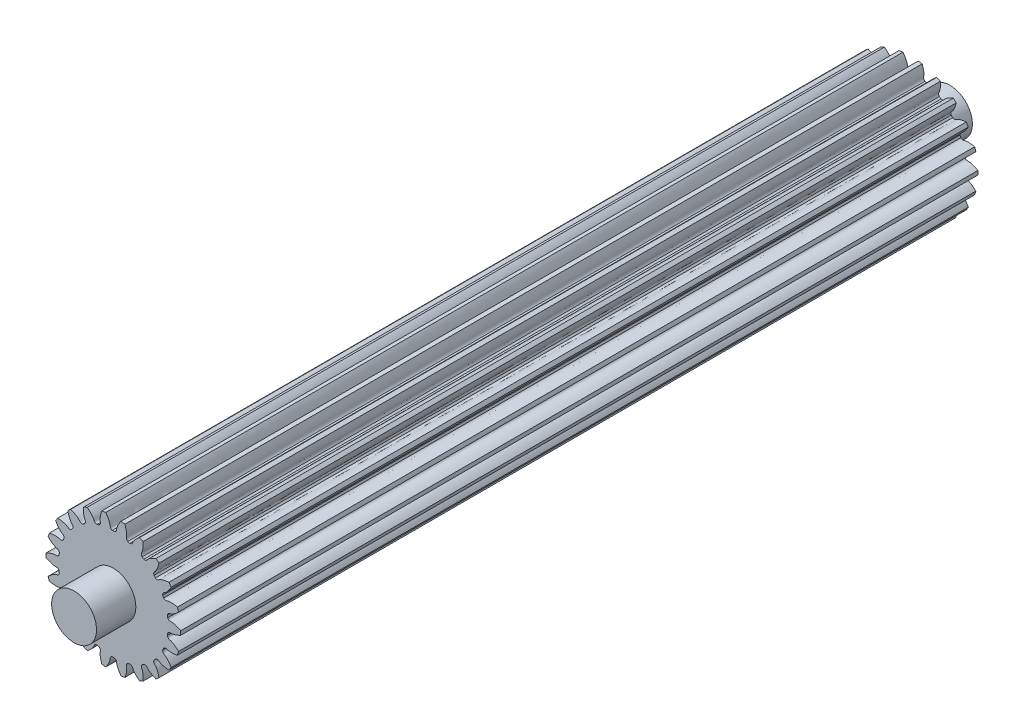
SolidWorks part; units mm, degrees
ref_plane "前视基准面" through (0, 0, 0) normal (0, 0, 1) x (1, 0, 0)
ref_plane "上视基准面" through (0, 0, 0) normal (0, 1, 0) x (1, 0, 0)
ref_plane "右视基准面" through (0, 0, 0) normal (1, 0, 0) x (0, 0, -1)
sketch "草图1" plane through (0, 0, 0) normal (0, 0, 1) x (1, 0, 0)
  circle A0 centre (0, 0) radius 12
extrude "凸台-拉伸1" add sketch "草图1" along normal blind 30
ref_axis "基准轴1" through (0, 0, -1.5) along (0, 0, 1)
sketch "草图2" plane through (0, 0, 0) normal (0, 0, 1) x (1, 0, 0)
  line L0 (0, 0) -> (0, 12) construction
  circle A0 centre (0, 0) radius 12 construction
  arc A1 (0.1857, 9.7482) -> (-0.1857, 9.7482) centre (0, 0) ccw
  arc A2 (3.0856, 13.5599) -> (-3.0856, 13.5599) centre (0, 0) ccw
  spline S0 degree 3 poles (0.1857, 9.7482) (0.5882, 9.8762) (0.5483, 10.1518) (0.5996, 10.4216) (0.606, 10.4519) (0.6139, 10.4862) (0.6235, 10.5243) (0.6349, 10.5661) (0.6484, 10.6117) (0.664, 10.661) (0.6819, 10.7139) (0.7023, 10.7703) (0.7253, 10.8301) (0.7511, 10.8933) (0.7797, 10.9597) (0.8114, 11.0293) (0.8462, 11.1021) (0.8843, 11.1778) (0.9259, 11.2563) (0.9711, 11.3377) (1.0199, 11.4217) (1.0726, 11.5082) (1.1292, 11.5972) (1.1899, 11.6884) (1.2547, 11.7818) (1.3238, 11.8773) (1.3973, 11.9746) (1.4753, 12.0737) (1.5579, 12.1744) (1.6452, 12.2766) (1.7372, 12.3802) (1.8341, 12.4849) (1.9359, 12.5906) (2.0428, 12.6972) (2.1547, 12.8044) (2.2718, 12.9123) (2.3942, 13.0205) (2.5218, 13.1289) (2.6548, 13.2373) (2.8415, 13.3834) (2.9864, 13.49) (3.0856, 13.5599) knots 0 0 0 0 0.157021 0.162531 0.168888 0.176093 0.184146 0.193046 0.202794 0.213389 0.224833 0.237123 0.250262 0.264248 0.279082 0.294763 0.311292 0.328669 0.346893 0.365965 0.385884 0.406652 0.428266 0.450729 0.474039 0.498197 0.523202 0.549055 0.575756 0.603304 0.6317 0.660944 0.691035 0.721974 0.75376 0.786395 0.819876 0.854206 0.889383 0.925408 1 1 1 1
  spline S1 degree 3 poles (-0.1857, 9.7482) (-0.5882, 9.8762) (-0.5483, 10.1518) (-0.5996, 10.4216) (-0.606, 10.4519) (-0.6139, 10.4862) (-0.6235, 10.5243) (-0.6349, 10.5661) (-0.6484, 10.6117) (-0.664, 10.661) (-0.6819, 10.7139) (-0.7023, 10.7703) (-0.7253, 10.8301) (-0.7511, 10.8933) (-0.7797, 10.9597) (-0.8114, 11.0293) (-0.8462, 11.1021) (-0.8843, 11.1778) (-0.9259, 11.2563) (-0.9711, 11.3377) (-1.0199, 11.4217) (-1.0726, 11.5082) (-1.1292, 11.5972) (-1.1899, 11.6884) (-1.2547, 11.7818) (-1.3238, 11.8773) (-1.3973, 11.9746) (-1.4753, 12.0737) (-1.5579, 12.1744) (-1.6452, 12.2766) (-1.7372, 12.3802) (-1.8341, 12.4849) (-1.9359, 12.5906) (-2.0428, 12.6972) (-2.1547, 12.8044) (-2.2718, 12.9123) (-2.3942, 13.0205) (-2.5218, 13.1289) (-2.6548, 13.2373) (-2.8415, 13.3834) (-2.9864, 13.49) (-3.0856, 13.5599) knots 0 0 0 0 0.157021 0.162531 0.168888 0.176093 0.184146 0.193046 0.202794 0.213389 0.224833 0.237123 0.250262 0.264248 0.279082 0.294763 0.311292 0.328669 0.346893 0.365965 0.385884 0.406652 0.428266 0.450729 0.474039 0.498197 0.523202 0.549055 0.575756 0.603304 0.6317 0.660944 0.691035 0.721974 0.75376 0.786395 0.819876 0.854206 0.889383 0.925408 1 1 1 1
extrude "切除-拉伸1" cut sketch "草图2" along normal through all
pattern_circular "阵列(圆周)1" count 22 every 16.364 about axis through (0, 0, -1.5) along (0, 0, 1) of "切除-拉伸1"
sketch "草图3" plane through (0, 0, 0) normal (0, 0, 1) x (1, 0, 0)
  circle A0 centre (0, 0) radius 11 construction
  dimension "Dn" = 22
sketch "草图4" plane through (0, 0, 0) normal (0, 0, -1) x (-1, 0, 0)
  arc A45 (2.9245, 9.3011) -> (2.5682, 9.4057) centre (0, 0) ccw
  arc A46 (2.0557, 11.8226) -> (1.3584, 11.9229) centre (0, 0) ccw
  arc A47 (0.1857, 9.7482) -> (-0.1857, 9.7482) centre (0, 0) ccw
  arc A48 (-1.3584, 11.9229) -> (-2.0557, 11.8226) centre (0, 0) ccw
  arc A49 (-2.5682, 9.4057) -> (-2.9245, 9.3011) centre (0, 0) ccw
  arc A50 (-4.6624, 11.0572) -> (-5.3032, 10.7646) centre (0, 0) ccw
  arc A51 (-5.1141, 8.3011) -> (-5.4265, 8.1004) centre (0, 0) ccw
  arc A52 (-7.5887, 9.2958) -> (-8.1211, 8.8344) centre (0, 0) ccw
  arc A53 (-7.2456, 6.5241) -> (-7.4888, 6.2434) centre (0, 0) ccw
  arc A54 (-9.9003, 6.7812) -> (-10.2811, 6.1886) centre (0, 0) ccw
  arc A55 (-8.7902, 4.2184) -> (-8.9444, 3.8807) centre (0, 0) ccw
  arc A56 (-11.4097, 3.7173) -> (-11.6082, 3.0414) centre (0, 0) ccw
  arc A57 (-9.6226, 1.5711) -> (-9.6754, 1.2035) centre (0, 0) ccw
  arc A58 (-11.9948, 0.3522) -> (-11.9948, -0.3522) centre (0, 0) ccw
  arc A59 (-9.6754, -1.2035) -> (-9.6226, -1.5711) centre (0, 0) ccw
  arc A60 (-11.6082, -3.0414) -> (-11.4097, -3.7173) centre (0, 0) ccw
  arc A61 (-8.9444, -3.8807) -> (-8.7902, -4.2184) centre (0, 0) ccw
  arc A62 (-10.2811, -6.1886) -> (-9.9003, -6.7812) centre (0, 0) ccw
  arc A63 (-7.4888, -6.2434) -> (-7.2456, -6.5241) centre (0, 0) ccw
  arc A64 (-8.1211, -8.8344) -> (-7.5887, -9.2958) centre (0, 0) ccw
  arc A65 (-5.4265, -8.1004) -> (-5.1141, -8.3011) centre (0, 0) ccw
  arc A66 (-5.3032, -10.7646) -> (-4.6624, -11.0572) centre (0, 0) ccw
  arc A67 (-2.9245, -9.3011) -> (-2.5682, -9.4057) centre (0, 0) ccw
  arc A68 (-2.0557, -11.8226) -> (-1.3584, -11.9229) centre (0, 0) ccw
  arc A69 (-0.1857, -9.7482) -> (0.1857, -9.7482) centre (0, 0) ccw
  arc A70 (1.3584, -11.9229) -> (2.0557, -11.8226) centre (0, 0) ccw
  arc A71 (2.5682, -9.4057) -> (2.9245, -9.3011) centre (0, 0) ccw
  arc A72 (4.6624, -11.0572) -> (5.3032, -10.7646) centre (0, 0) ccw
  arc A73 (5.1141, -8.3011) -> (5.4265, -8.1004) centre (0, 0) ccw
  arc A74 (7.5887, -9.2958) -> (8.1211, -8.8344) centre (0, 0) ccw
  arc A75 (7.2456, -6.5241) -> (7.4888, -6.2434) centre (0, 0) ccw
  arc A76 (9.9003, -6.7812) -> (10.2811, -6.1886) centre (0, 0) ccw
  arc A77 (8.7902, -4.2184) -> (8.9444, -3.8807) centre (0, 0) ccw
  arc A78 (11.4097, -3.7173) -> (11.6082, -3.0414) centre (0, 0) ccw
  arc A79 (9.6226, -1.5711) -> (9.6754, -1.2035) centre (0, 0) ccw
  arc A80 (11.9948, -0.3522) -> (11.9948, 0.3522) centre (0, 0) ccw
  arc A81 (9.6754, 1.2035) -> (9.6226, 1.5711) centre (0, 0) ccw
  arc A82 (11.6082, 3.0414) -> (11.4097, 3.7173) centre (0, 0) ccw
  arc A83 (8.9444, 3.8807) -> (8.7902, 4.2184) centre (0, 0) ccw
  arc A84 (10.2811, 6.1886) -> (9.9003, 6.7812) centre (0, 0) ccw
  arc A85 (7.4888, 6.2434) -> (7.2456, 6.5241) centre (0, 0) ccw
  arc A86 (8.1211, 8.8344) -> (7.5887, 9.2958) centre (0, 0) ccw
  arc A87 (5.4265, 8.1004) -> (5.1141, 8.3011) centre (0, 0) ccw
  arc A88 (5.3032, 10.7646) -> (4.6624, 11.0572) centre (0, 0) ccw
  arc A89 (2.9245, 9.3011) -> (2.5682, 9.4057) centre (0, 0) ccw
  arc A90 (2.0557, 11.8226) -> (1.3584, 11.9229) centre (0, 0) ccw
  arc A91 (0.1857, 9.7482) -> (-0.1857, 9.7482) centre (0, 0) ccw
  arc A92 (-1.3584, 11.9229) -> (-2.0557, 11.8226) centre (0, 0) ccw
  arc A93 (-2.5682, 9.4057) -> (-2.9245, 9.3011) centre (0, 0) ccw
  arc A94 (-4.6624, 11.0572) -> (-5.3032, 10.7646) centre (0, 0) ccw
  arc A95 (-5.1141, 8.3011) -> (-5.4265, 8.1004) centre (0, 0) ccw
  arc A96 (-7.5887, 9.2958) -> (-8.1211, 8.8344) centre (0, 0) ccw
  arc A97 (-7.2456, 6.5241) -> (-7.4888, 6.2434) centre (0, 0) ccw
  arc A98 (-9.9003, 6.7812) -> (-10.2811, 6.1886) centre (0, 0) ccw
  arc A99 (-8.7902, 4.2184) -> (-8.9444, 3.8807) centre (0, 0) ccw
  arc A100 (-11.4097, 3.7173) -> (-11.6082, 3.0414) centre (0, 0) ccw
  arc A101 (-9.6226, 1.5711) -> (-9.6754, 1.2035) centre (0, 0) ccw
  arc A102 (-11.9948, 0.3522) -> (-11.9948, -0.3522) centre (0, 0) ccw
  arc A103 (-9.6754, -1.2035) -> (-9.6226, -1.5711) centre (0, 0) ccw
  arc A104 (-11.6082, -3.0414) -> (-11.4097, -3.7173) centre (0, 0) ccw
  arc A105 (-8.9444, -3.8807) -> (-8.7902, -4.2184) centre (0, 0) ccw
  arc A106 (-10.2811, -6.1886) -> (-9.9003, -6.7812) centre (0, 0) ccw
  arc A107 (-7.4888, -6.2434) -> (-7.2456, -6.5241) centre (0, 0) ccw
  arc A108 (-8.1211, -8.8344) -> (-7.5887, -9.2958) centre (0, 0) ccw
  arc A109 (-5.4265, -8.1004) -> (-5.1141, -8.3011) centre (0, 0) ccw
  arc A110 (-5.3032, -10.7646) -> (-4.6624, -11.0572) centre (0, 0) ccw
  arc A111 (-2.9245, -9.3011) -> (-2.5682, -9.4057) centre (0, 0) ccw
  arc A112 (-2.0557, -11.8226) -> (-1.3584, -11.9229) centre (0, 0) ccw
  arc A113 (-0.1857, -9.7482) -> (0.1857, -9.7482) centre (0, 0) ccw
  arc A114 (1.3584, -11.9229) -> (2.0557, -11.8226) centre (0, 0) ccw
  arc A115 (2.5682, -9.4057) -> (2.9245, -9.3011) centre (0, 0) ccw
  arc A116 (4.6624, -11.0572) -> (5.3032, -10.7646) centre (0, 0) ccw
  arc A117 (5.1141, -8.3011) -> (5.4265, -8.1004) centre (0, 0) ccw
  arc A118 (7.5887, -9.2958) -> (8.1211, -8.8344) centre (0, 0) ccw
  arc A119 (7.2456, -6.5241) -> (7.4888, -6.2434) centre (0, 0) ccw
  arc A120 (9.9003, -6.7812) -> (10.2811, -6.1886) centre (0, 0) ccw
  arc A121 (8.7902, -4.2184) -> (8.9444, -3.8807) centre (0, 0) ccw
  arc A122 (11.4097, -3.7173) -> (11.6082, -3.0414) centre (0, 0) ccw
  arc A123 (9.6226, -1.5711) -> (9.6754, -1.2035) centre (0, 0) ccw
  arc A124 (11.9948, -0.3522) -> (11.9948, 0.3522) centre (0, 0) ccw
  arc A125 (9.6754, 1.2035) -> (9.6226, 1.5711) centre (0, 0) ccw
  arc A126 (11.6082, 3.0414) -> (11.4097, 3.7173) centre (0, 0) ccw
  arc A127 (8.9444, 3.8807) -> (8.7902, 4.2184) centre (0, 0) ccw
  arc A128 (10.2811, 6.1886) -> (9.9003, 6.7812) centre (0, 0) ccw
  arc A129 (7.4888, 6.2434) -> (7.2456, 6.5241) centre (0, 0) ccw
  arc A130 (8.1211, 8.8344) -> (7.5887, 9.2958) centre (0, 0) ccw
  arc A131 (5.4265, 8.1004) -> (5.1141, 8.3011) centre (0, 0) ccw
  arc A132 (5.3032, 10.7646) -> (4.6624, 11.0572) centre (0, 0) ccw
  spline S44 degree 3 poles (-5627.2854, 2078.3938) (192.8946, -127.0066) (26.4411, 29.7149) (4.2738, 10.7434) (4.1283, 10.6084) (3.9999, 10.4794) (3.888, 10.3576) (3.7917, 10.2441) (3.7102, 10.1398) (3.6518, 10.0587) (3.6037, 9.9872) (3.5713, 9.9359) (3.5381, 9.8795) (3.5167, 9.8409) (0.8972, 4.7255) (36.3074, -19.3341) (-5049.4514, 3243.9843) knots -17.307157 -17.307157 -17.307157 -17.307157 0.549271 0.593348 0.634035 0.671331 0.705237 0.735752 0.762877 0.786611 0.797206 0.815854 0.823907 0.837469 0.842979 4.358372 4.358372 4.358372 4.358372 only from (4.6624, 11.0572) to (2.9245, 9.3011)
  spline S45 degree 3 poles (6000.7137, -0.9256) (-40.9919, 3.3645) (1.8001, 4.4607) (2.3619, 10.18) (2.3658, 10.2385) (2.3681, 10.3211) (2.3668, 10.4204) (2.3608, 10.536) (2.3486, 10.6678) (2.329, 10.8154) (2.3007, 10.9784) (2.2624, 11.1562) (2.213, 11.3485) (2.1511, 11.5544) (-7.9452, 40.8705) (-242.4769, -12.2249) (5863.0962, -1268.8283) knots -3.358181 -3.358181 -3.358181 -3.358181 0.157021 0.162531 0.176093 0.193046 0.213389 0.237123 0.264248 0.294763 0.328669 0.365965 0.406652 0.450729 0.498197 19.472301 19.472301 19.472301 19.472301 only from (2.5682, 9.4057) to (2.0557, 11.8226)
  spline S46 degree 3 poles (-5984.892, 408.8148) (220.863, -67.5173) (16.9983, 35.9606) (1.0739, 11.5123) (0.9723, 11.3417) (0.8855, 11.1818) (0.8124, 11.0334) (0.752, 10.8973) (0.7032, 10.7743) (0.6701, 10.6801) (0.644, 10.5979) (0.6274, 10.5396) (0.6113, 10.4761) (0.6018, 10.4331) (-0.4705, 4.7868) (40.2837, -8.322) (-5758.8491, 1689.9853) knots -17.307157 -17.307157 -17.307157 -17.307157 0.549271 0.593348 0.634035 0.671331 0.705237 0.735752 0.762877 0.786611 0.797206 0.815854 0.823907 0.837469 0.842979 4.358372 4.358372 4.358372 4.358372 only from (1.3584, 11.9229) to (0.1857, 9.7482)
  spline S47 degree 3 poles (5757.9034, 1689.7083) (-40.2793, -8.3206) (0.4704, 4.7871) (-0.6018, 10.4331) (-0.6145, 10.4903) (-0.6356, 10.5702) (-0.6648, 10.6651) (-0.7032, 10.7743) (-0.752, 10.8973) (-0.8124, 11.0334) (-0.8855, 11.1818) (-0.9723, 11.3417) (-1.0739, 11.5123) (-1.1913, 11.6924) (-19.1379, 36.9765) (-229.2107, -80.0433) (5983.0699, 434.3932) knots -3.358181 -3.358181 -3.358181 -3.358181 0.157021 0.162531 0.176093 0.193046 0.213389 0.237123 0.264248 0.294763 0.328669 0.365965 0.406652 0.450729 0.498197 19.472301 19.472301 19.472301 19.472301 only from (-0.1857, 9.7482) to (-1.3584, 11.9229)
  spline S48 degree 3 poles (-5857.6382, -1293.884) (230.9383, -2.5581) (6.1785, 39.2929) (-2.213, 11.3485) (-2.2624, 11.1562) (-2.3007, 10.9784) (-2.329, 10.8154) (-2.3486, 10.6678) (-2.3608, 10.536) (-2.366, 10.4362) (-2.3678, 10.3501) (-2.3674, 10.2894) (-2.3649, 10.224) (-2.3619, 10.18) (-1.8001, 4.4604) (40.9965, 3.3643) (-6001.6991, -0.9263) knots -17.307157 -17.307157 -17.307157 -17.307157 0.549271 0.593348 0.634035 0.671331 0.705237 0.735752 0.762877 0.786611 0.797206 0.815854 0.823907 0.837469 0.842979 4.358372 4.358372 4.358372 4.358372 only from (-2.0557, 11.8226) to (-2.5682, 9.4057)
  spline S49 degree 3 poles (5048.622, 3243.4521) (-36.3035, -19.3315) (-0.8973, 4.7258) (-3.5167, 9.8409) (-3.5451, 9.8922) (-3.5879, 9.963) (-3.6426, 10.0458) (-3.7102, 10.1398) (-3.7917, 10.2441) (-3.888, 10.3576) (-3.9999, 10.4794) (-4.1283, 10.6084) (-4.2738, 10.7434) (-4.4372, 10.8832) (-28.7802, 30.087) (-197.3753, -141.3771) (5618.3308, 2102.4228) knots -3.358181 -3.358181 -3.358181 -3.358181 0.157021 0.162531 0.176093 0.193046 0.213389 0.237123 0.264248 0.294763 0.328669 0.365965 0.406652 0.450729 0.498197 19.472301 19.472301 19.472301 19.472301 only from (-2.9245, 9.3011) to (-4.6624, 11.0572)
  spline S50 degree 3 poles (-5255.8335, -2891.76) (222.3043, 62.6084) (-5.1418, 39.442) (-5.3206, 10.2653) (-5.3138, 10.0669) (-5.3004, 9.8855) (-5.2817, 9.7211) (-5.2589, 9.574) (-5.2335, 9.4441) (-5.2104, 9.3469) (-5.1879, 9.2637) (-5.1704, 9.2057) (-5.1495, 9.1436) (-5.1343, 9.1022) (-2.9838, 3.7726) (38.388, 14.7781) (-5758.3272, -1691.7628) knots -17.307157 -17.307157 -17.307157 -17.307157 0.549271 0.593348 0.634035 0.671331 0.705237 0.735752 0.762877 0.786611 0.797206 0.815854 0.823907 0.837469 0.842979 4.358372 4.358372 4.358372 4.358372 only from (-5.3032, 10.7646) to (-5.1141, 8.3011)
  spline S51 degree 3 poles (3930.3313, 4534.4307) (-29.3867, -28.7763) (-2.1924, 4.2815) (-6.1468, 8.4515) (-6.1884, 8.4928) (-6.2494, 8.5486) (-6.3253, 8.6126) (-6.4166, 8.6838) (-6.5242, 8.7609) (-6.6486, 8.8427) (-6.7903, 8.928) (-6.9498, 9.0156) (-7.1274, 9.1041) (-7.3236, 9.1923) (-36.0908, 20.7599) (-149.5496, -191.2574) (4798.428, 3600.1266) knots -3.358181 -3.358181 -3.358181 -3.358181 0.157021 0.162531 0.176093 0.193046 0.213389 0.237123 0.264248 0.294763 0.328669 0.365965 0.406652 0.450729 0.498197 19.472301 19.472301 19.472301 19.472301 only from (-5.4265, 8.1004) to (-7.5887, 9.2958)
  spline S52 degree 3 poles (-4228.2323, -4255.3628) (195.6606, 122.7027) (-16.0457, 36.3957) (-7.9971, 8.3505) (-7.9348, 8.1621) (-7.8708, 7.9917) (-7.8065, 7.8393) (-7.7432, 7.7046) (-7.6822, 7.5871) (-7.6327, 7.5003) (-7.5876, 7.4269) (-7.5545, 7.3761) (-7.517, 7.3224) (-7.4907, 7.287) (-3.9258, 2.7791) (32.6696, 24.9947) (-5048.4498, -3245.5427) knots -17.307157 -17.307157 -17.307157 -17.307157 0.549271 0.593348 0.634035 0.671331 0.705237 0.735752 0.762877 0.786611 0.797206 0.815854 0.823907 0.837469 0.842979 4.358372 4.358372 4.358372 4.358372 only from (-8.1211, 8.8344) to (-7.2456, 6.5241)
  spline S53 degree 3 poles (2493.6285, 5458.0567) (-20.0891, -35.8899) (-3.3098, 3.4905) (-8.2789, 6.3774) (-8.3304, 6.4053) (-8.4047, 6.4416) (-8.4955, 6.4817) (-8.6032, 6.5243) (-8.7281, 6.5679) (-8.8705, 6.6114) (-9.0305, 6.6533) (-9.2082, 6.6924) (-9.4036, 6.7273) (-9.6167, 6.7566) (-40.4777, 9.751) (-89.6084, -225.6431) (3589.785, 4806.1696) knots -3.358181 -3.358181 -3.358181 -3.358181 0.157021 0.162531 0.176093 0.193046 0.213389 0.237123 0.264248 0.294763 0.328669 0.365965 0.406652 0.450729 0.498197 19.472301 19.472301 19.472301 19.472301 only from (-7.4888, 6.2434) to (-9.9003, 6.7812)
  spline S54 degree 3 poles (-2858.085, -5274.2214) (153.1657, 172.8563) (-25.6495, 30.4008) (-10.0258, 5.7592) (-9.9129, 5.596) (-9.8035, 5.4506) (-9.6989, 5.3224) (-9.6002, 5.211) (-9.5086, 5.1155) (-9.4366, 5.0462) (-9.3727, 4.9884) (-9.3266, 4.949) (-9.2755, 4.908) (-9.2403, 4.8814) (-4.5497, 1.5605) (24.3044, 33.1863) (-3929.5771, -4536.3881) knots -17.307157 -17.307157 -17.307157 -17.307157 0.549271 0.593348 0.634035 0.671331 0.705237 0.735752 0.762877 0.786611 0.797206 0.815854 0.823907 0.837469 0.842979 4.358372 4.358372 4.358372 4.358372 only from (-10.2811, 6.1886) to (-8.7902, 4.2184)
  spline S55 degree 3 poles (854.9067, 5939.5034) (-9.164, -40.0958) (-4.1591, 2.4166) (-9.7402, 3.7867) (-9.7976, 3.7989) (-9.8791, 3.8128) (-9.9775, 3.8257) (-10.0928, 3.8362) (-10.225, 3.8429) (-10.3738, 3.8445) (-10.5392, 3.8396) (-10.7207, 3.8271) (-10.918, 3.8055) (-11.1307, 3.7736) (-41.5852, -2.0478) (-22.4076, -241.7486) (2090.3191, 5622.8452) knots -3.358181 -3.358181 -3.358181 -3.358181 0.157021 0.162531 0.176093 0.193046 0.213389 0.237123 0.264248 0.294763 0.328669 0.365965 0.406652 0.450729 0.498197 19.472301 19.472301 19.472301 19.472301 only from (-8.9444, 3.8807) to (-11.4097, 3.7173)
  spline S56 degree 3 poles (-1256.3926, -5865.794) (98.2621, 209.0062) (-33.1754, 21.943) (-11.2422, 2.7013) (-11.0879, 2.5765) (-10.942, 2.4678) (-10.8055, 2.3743) (-10.6794, 2.2952) (-10.5646, 2.2294) (-10.476, 2.1832) (-10.3984, 2.1457) (-10.3431, 2.1209) (-10.2825, 2.096) (-10.2412, 2.0804) (-4.8051, 0.2155) (13.9703, 38.6894) (-2492.3534, -5459.7223) knots -17.307157 -17.307157 -17.307157 -17.307157 0.549271 0.593348 0.634035 0.671331 0.705237 0.735752 0.762877 0.786611 0.797206 0.815854 0.823907 0.837469 0.842979 4.358372 4.358372 4.358372 4.358372 only from (-11.6082, 3.0414) to (-9.6226, 1.5711)
  spline S57 degree 3 poles (-853.0745, 5939.7668) (2.5035, -41.0535) (-4.6715, 1.1469) (-10.4125, 0.8891) (-10.4709, 0.8847) (-10.5531, 0.8751) (-10.6512, 0.8598) (-10.7647, 0.8373) (-10.8934, 0.8065) (-11.0367, 0.7661) (-11.194, 0.7149) (-11.3647, 0.6517) (-11.5479, 0.5754) (-11.743, 0.4849) (-39.3238, -13.6808) (46.6085, -238.269) (421.5079, 5983.9914) knots -3.358181 -3.358181 -3.358181 -3.358181 0.157021 0.162531 0.176093 0.193046 0.213389 0.237123 0.264248 0.294763 0.328669 0.365965 0.406652 0.450729 0.498197 19.472301 19.472301 19.472301 19.472301 only from (-9.6754, 1.2035) to (-11.9948, 0.3522)
  spline S58 degree 3 poles (447.0853, -5982.1548) (35.398, 228.2236) (-38.0137, 11.7076) (-11.5479, -0.5754) (-11.3647, -0.6517) (-11.194, -0.7149) (-11.0367, -0.7661) (-10.8934, -0.8065) (-10.7647, -0.8373) (-10.6667, -0.8567) (-10.5817, -0.8708) (-10.5216, -0.879) (-10.4565, -0.8858) (-10.4125, -0.8891) (-4.6712, -1.147) (2.5043, 41.058) (-853.214, -5940.7423) knots -17.307157 -17.307157 -17.307157 -17.307157 0.549271 0.593348 0.634035 0.671331 0.705237 0.735752 0.762877 0.786611 0.797206 0.815854 0.823907 0.837469 0.842979 4.358372 4.358372 4.358372 4.358372 only from (-11.9948, -0.3522) to (-9.6754, -1.2035)
  spline S59 degree 3 poles (-2491.9446, 5458.8257) (13.9682, -38.6852) (-4.8054, -0.2156) (-10.2412, -2.0804) (-10.296, -2.1012) (-10.3722, -2.1335) (-10.4619, -2.1758) (-10.5646, -2.2294) (-10.6794, -2.2952) (-10.8055, -2.3743) (-10.942, -2.4678) (-11.0879, -2.5765) (-11.2422, -2.7014) (-11.4039, -2.8432) (-33.8766, -24.2054) (111.8487, -215.4863) (-1281.4514, 5860.3502) knots -3.358181 -3.358181 -3.358181 -3.358181 0.157021 0.162531 0.176093 0.193046 0.213389 0.237123 0.264248 0.294763 0.328669 0.365965 0.406652 0.450729 0.498197 19.472301 19.472301 19.472301 19.472301 only from (-9.6226, -1.5711) to (-11.6082, -3.0414)
  spline S60 degree 3 poles (2114.343, -5613.877) (-30.3339, 228.9517) (-39.7723, 0.5237) (-10.918, -3.8055) (-10.7207, -3.8271) (-10.5392, -3.8396) (-10.3738, -3.8445) (-10.225, -3.8429) (-10.0928, -3.8362) (-9.9933, -3.8272) (-9.9078, -3.8167) (-9.8478, -3.8076) (-9.7834, -3.7958) (-9.7402, -3.7867) (-4.1588, -2.4165) (-9.1645, 40.1005) (855.0477, -5940.4787) knots -17.307157 -17.307157 -17.307157 -17.307157 0.549271 0.593348 0.634035 0.671331 0.705237 0.735752 0.762877 0.786611 0.797206 0.815854 0.823907 0.837469 0.842979 4.358372 4.358372 4.358372 4.358372 only from (-11.4097, -3.7173) to (-8.9444, -3.8807)
  spline S61 degree 3 poles (-3928.9323, 4535.6429) (24.3013, -33.1829) (-4.55, -1.5607) (-9.2403, -4.8814) (-9.287, -4.9168) (-9.351, -4.9692) (-9.4251, -5.0352) (-9.5086, -5.1155) (-9.6002, -5.211) (-9.6989, -5.3224) (-9.8035, -5.4506) (-9.9129, -5.596) (-10.0258, -5.7592) (-10.1409, -5.9408) (-25.6849, -32.769) (168.0275, -175.2462) (-2880.595, 5261.9383) knots -3.358181 -3.358181 -3.358181 -3.358181 0.157021 0.162531 0.176093 0.193046 0.213389 0.237123 0.264248 0.294763 0.328669 0.365965 0.406652 0.450729 0.498197 19.472301 19.472301 19.472301 19.472301 only from (-8.7902, -4.2184) to (-10.2811, -6.1886)
  spline S62 degree 3 poles (3610.3092, -4790.7963) (-93.6083, 211.1315) (-38.3087, -10.7027) (-9.4036, -6.7273) (-9.2082, -6.6924) (-9.0305, -6.6533) (-8.8705, -6.6114) (-8.7281, -6.5679) (-8.6032, -6.5243) (-8.5102, -6.4876) (-8.4311, -6.4535) (-8.3761, -6.4279) (-8.3177, -6.3984) (-8.2789, -6.3774) (-3.3095, -3.4903) (-20.0909, 35.8942) (2494.0385, -5458.9528) knots -17.307157 -17.307157 -17.307157 -17.307157 0.549271 0.593348 0.634035 0.671331 0.705237 0.735752 0.762877 0.786611 0.797206 0.815854 0.823907 0.837469 0.842979 4.358372 4.358372 4.358372 4.358372 only from (-9.9003, -6.7812) to (-7.4888, -6.2434)
  spline S63 degree 3 poles (-5047.6212, 3245.0094) (32.6656, -24.9923) (-3.926, -2.7794) (-7.4907, -7.287) (-7.5256, -7.3341) (-7.5722, -7.4024) (-7.6248, -7.4866) (-7.6822, -7.5871) (-7.7432, -7.7046) (-7.8065, -7.8393) (-7.8708, -7.9917) (-7.9348, -8.1621) (-7.9971, -8.3505) (-8.0564, -8.5572) (-15.4124, -38.6779) (210.5938, -120.8087) (-4246.37, 4237.2354) knots -3.358181 -3.358181 -3.358181 -3.358181 0.157021 0.162531 0.176093 0.193046 0.213389 0.237123 0.264248 0.294763 0.328669 0.365965 0.406652 0.450729 0.498197 19.472301 19.472301 19.472301 19.472301 only from (-7.2456, -6.5241) to (-8.1211, -8.8344)
  spline S64 degree 3 poles (4813.7896, -3579.5938) (-149.2992, 176.2067) (-33.7417, -21.062) (-7.1274, -9.1041) (-6.9498, -9.0156) (-6.7903, -8.928) (-6.6486, -8.8427) (-6.5242, -8.7609) (-6.4166, -8.6838) (-6.3378, -8.6224) (-6.2715, -8.5674) (-6.2259, -8.5273) (-6.1781, -8.4826) (-6.1468, -8.4515) (-2.1921, -4.2813) (-29.3896, 28.7799) (3930.9771, -4535.175) knots -17.307157 -17.307157 -17.307157 -17.307157 0.549271 0.593348 0.634035 0.671331 0.705237 0.735752 0.762877 0.786611 0.797206 0.815854 0.823907 0.837469 0.842979 4.358372 4.358372 4.358372 4.358372 only from (-7.5887, -9.2958) to (-5.4265, -8.1004)
  spline S65 degree 3 poles (-5757.3819, 1691.4845) (38.3836, -14.7769) (-2.9839, -3.7729) (-5.1343, -9.1022) (-5.1545, -9.1572) (-5.18, -9.2359) (-5.2067, -9.3315) (-5.2335, -9.4441) (-5.2589, -9.574) (-5.2817, -9.7211) (-5.3004, -9.8855) (-5.3138, -10.0669) (-5.3206, -10.2653) (-5.3192, -10.4804) (-3.8912, -41.4534) (236.099, -56.584) (-5268.1294, 2869.2569) knots -3.358181 -3.358181 -3.358181 -3.358181 0.157021 0.162531 0.176093 0.193046 0.213389 0.237123 0.264248 0.294763 0.328669 0.365965 0.406652 0.450729 0.498197 19.472301 19.472301 19.472301 19.472301 only from (-5.1141, -8.3011) to (-5.3032, -10.7646)
  spline S66 degree 3 poles (5627.2854, -2078.3938) (-192.8946, 127.0066) (-26.4411, -29.7149) (-4.2738, -10.7434) (-4.1283, -10.6084) (-3.9999, -10.4794) (-3.888, -10.3576) (-3.7917, -10.2441) (-3.7102, -10.1398) (-3.6518, -10.0587) (-3.6037, -9.9872) (-3.5713, -9.9359) (-3.5381, -9.8795) (-3.5167, -9.8409) (-0.8972, -4.7255) (-36.3074, 19.3341) (5049.4514, -3243.9843) knots -17.307157 -17.307157 -17.307157 -17.307157 0.549271 0.593348 0.634035 0.671331 0.705237 0.735752 0.762877 0.786611 0.797206 0.815854 0.823907 0.837469 0.842979 4.358372 4.358372 4.358372 4.358372 only from (-4.6624, -11.0572) to (-2.9245, -9.3011)
  spline S67 degree 3 poles (-6000.7137, 0.9256) (40.9919, -3.3645) (-1.8001, -4.4607) (-2.3619, -10.18) (-2.3658, -10.2385) (-2.3681, -10.3211) (-2.3668, -10.4204) (-2.3608, -10.536) (-2.3486, -10.6678) (-2.329, -10.8154) (-2.3007, -10.9784) (-2.2624, -11.1562) (-2.213, -11.3485) (-2.1511, -11.5544) (7.9452, -40.8705) (242.4769, 12.2249) (-5863.0962, 1268.8283) knots -3.358181 -3.358181 -3.358181 -3.358181 0.157021 0.162531 0.176093 0.193046 0.213389 0.237123 0.264248 0.294763 0.328669 0.365965 0.406652 0.450729 0.498197 19.472301 19.472301 19.472301 19.472301 only from (-2.5682, -9.4057) to (-2.0557, -11.8226)
  spline S68 degree 3 poles (5984.892, -408.8148) (-220.863, 67.5173) (-16.9983, -35.9606) (-1.0739, -11.5123) (-0.9723, -11.3417) (-0.8855, -11.1818) (-0.8124, -11.0334) (-0.752, -10.8973) (-0.7032, -10.7743) (-0.6701, -10.6801) (-0.644, -10.5979) (-0.6274, -10.5396) (-0.6113, -10.4761) (-0.6018, -10.4331) (0.4705, -4.7868) (-40.2837, 8.322) (5758.8491, -1689.9853) knots -17.307157 -17.307157 -17.307157 -17.307157 0.549271 0.593348 0.634035 0.671331 0.705237 0.735752 0.762877 0.786611 0.797206 0.815854 0.823907 0.837469 0.842979 4.358372 4.358372 4.358372 4.358372 only from (-1.3584, -11.9229) to (-0.1857, -9.7482)
  spline S69 degree 3 poles (-5757.9034, -1689.7083) (40.2793, 8.3206) (-0.4704, -4.7871) (0.6018, -10.4331) (0.6145, -10.4903) (0.6356, -10.5702) (0.6648, -10.6651) (0.7032, -10.7743) (0.752, -10.8973) (0.8124, -11.0334) (0.8855, -11.1818) (0.9723, -11.3417) (1.0739, -11.5123) (1.1913, -11.6924) (19.1379, -36.9765) (229.2107, 80.0433) (-5983.0699, -434.3932) knots -3.358181 -3.358181 -3.358181 -3.358181 0.157021 0.162531 0.176093 0.193046 0.213389 0.237123 0.264248 0.294763 0.328669 0.365965 0.406652 0.450729 0.498197 19.472301 19.472301 19.472301 19.472301 only from (0.1857, -9.7482) to (1.3584, -11.9229)
  spline S70 degree 3 poles (5857.6382, 1293.884) (-230.9383, 2.5581) (-6.1785, -39.2929) (2.213, -11.3485) (2.2624, -11.1562) (2.3007, -10.9784) (2.329, -10.8154) (2.3486, -10.6678) (2.3608, -10.536) (2.366, -10.4362) (2.3678, -10.3501) (2.3674, -10.2894) (2.3649, -10.224) (2.3619, -10.18) (1.8001, -4.4604) (-40.9965, -3.3643) (6001.6991, 0.9263) knots -17.307157 -17.307157 -17.307157 -17.307157 0.549271 0.593348 0.634035 0.671331 0.705237 0.735752 0.762877 0.786611 0.797206 0.815854 0.823907 0.837469 0.842979 4.358372 4.358372 4.358372 4.358372 only from (2.0557, -11.8226) to (2.5682, -9.4057)
  spline S71 degree 3 poles (-5048.622, -3243.4521) (36.3035, 19.3315) (0.8973, -4.7258) (3.5167, -9.8409) (3.5451, -9.8922) (3.5879, -9.963) (3.6426, -10.0458) (3.7102, -10.1398) (3.7917, -10.2441) (3.888, -10.3576) (3.9999, -10.4794) (4.1283, -10.6084) (4.2738, -10.7434) (4.4372, -10.8832) (28.7802, -30.087) (197.3753, 141.3771) (-5618.3308, -2102.4228) knots -3.358181 -3.358181 -3.358181 -3.358181 0.157021 0.162531 0.176093 0.193046 0.213389 0.237123 0.264248 0.294763 0.328669 0.365965 0.406652 0.450729 0.498197 19.472301 19.472301 19.472301 19.472301 only from (2.9245, -9.3011) to (4.6624, -11.0572)
  spline S72 degree 3 poles (5255.8335, 2891.76) (-222.3043, -62.6084) (5.1418, -39.442) (5.3206, -10.2653) (5.3138, -10.0669) (5.3004, -9.8855) (5.2817, -9.7211) (5.2589, -9.574) (5.2335, -9.4441) (5.2104, -9.3469) (5.1879, -9.2637) (5.1704, -9.2057) (5.1495, -9.1436) (5.1343, -9.1022) (2.9838, -3.7726) (-38.388, -14.7781) (5758.3272, 1691.7628) knots -17.307157 -17.307157 -17.307157 -17.307157 0.549271 0.593348 0.634035 0.671331 0.705237 0.735752 0.762877 0.786611 0.797206 0.815854 0.823907 0.837469 0.842979 4.358372 4.358372 4.358372 4.358372 only from (5.3032, -10.7646) to (5.1141, -8.3011)
  spline S73 degree 3 poles (-3930.3313, -4534.4307) (29.3867, 28.7763) (2.1924, -4.2815) (6.1468, -8.4515) (6.1884, -8.4928) (6.2494, -8.5486) (6.3253, -8.6126) (6.4166, -8.6838) (6.5242, -8.7609) (6.6486, -8.8427) (6.7903, -8.928) (6.9498, -9.0156) (7.1274, -9.1041) (7.3236, -9.1923) (36.0908, -20.7599) (149.5496, 191.2574) (-4798.428, -3600.1266) knots -3.358181 -3.358181 -3.358181 -3.358181 0.157021 0.162531 0.176093 0.193046 0.213389 0.237123 0.264248 0.294763 0.328669 0.365965 0.406652 0.450729 0.498197 19.472301 19.472301 19.472301 19.472301 only from (5.4265, -8.1004) to (7.5887, -9.2958)
  spline S74 degree 3 poles (4228.2323, 4255.3628) (-195.6606, -122.7027) (16.0457, -36.3957) (7.9971, -8.3505) (7.9348, -8.1621) (7.8708, -7.9917) (7.8065, -7.8393) (7.7432, -7.7046) (7.6822, -7.5871) (7.6327, -7.5003) (7.5876, -7.4269) (7.5545, -7.3761) (7.517, -7.3224) (7.4907, -7.287) (3.9258, -2.7791) (-32.6696, -24.9947) (5048.4498, 3245.5427) knots -17.307157 -17.307157 -17.307157 -17.307157 0.549271 0.593348 0.634035 0.671331 0.705237 0.735752 0.762877 0.786611 0.797206 0.815854 0.823907 0.837469 0.842979 4.358372 4.358372 4.358372 4.358372 only from (8.1211, -8.8344) to (7.2456, -6.5241)
  spline S75 degree 3 poles (-2493.6285, -5458.0567) (20.0891, 35.8899) (3.3098, -3.4905) (8.2789, -6.3774) (8.3304, -6.4053) (8.4047, -6.4416) (8.4955, -6.4817) (8.6032, -6.5243) (8.7281, -6.5679) (8.8705, -6.6114) (9.0305, -6.6533) (9.2082, -6.6924) (9.4036, -6.7273) (9.6167, -6.7566) (40.4777, -9.751) (89.6084, 225.6431) (-3589.785, -4806.1696) knots -3.358181 -3.358181 -3.358181 -3.358181 0.157021 0.162531 0.176093 0.193046 0.213389 0.237123 0.264248 0.294763 0.328669 0.365965 0.406652 0.450729 0.498197 19.472301 19.472301 19.472301 19.472301 only from (7.4888, -6.2434) to (9.9003, -6.7812)
  spline S76 degree 3 poles (2858.085, 5274.2214) (-153.1657, -172.8563) (25.6495, -30.4008) (10.0258, -5.7592) (9.9129, -5.596) (9.8035, -5.4506) (9.6989, -5.3224) (9.6002, -5.211) (9.5086, -5.1155) (9.4366, -5.0462) (9.3727, -4.9884) (9.3266, -4.949) (9.2755, -4.908) (9.2403, -4.8814) (4.5497, -1.5605) (-24.3044, -33.1863) (3929.5771, 4536.3881) knots -17.307157 -17.307157 -17.307157 -17.307157 0.549271 0.593348 0.634035 0.671331 0.705237 0.735752 0.762877 0.786611 0.797206 0.815854 0.823907 0.837469 0.842979 4.358372 4.358372 4.358372 4.358372 only from (10.2811, -6.1886) to (8.7902, -4.2184)
  spline S77 degree 3 poles (-854.9067, -5939.5034) (9.164, 40.0958) (4.1591, -2.4166) (9.7402, -3.7867) (9.7976, -3.7989) (9.8791, -3.8128) (9.9775, -3.8257) (10.0928, -3.8362) (10.225, -3.8429) (10.3738, -3.8445) (10.5392, -3.8396) (10.7207, -3.8271) (10.918, -3.8055) (11.1307, -3.7736) (41.5852, 2.0478) (22.4076, 241.7486) (-2090.3191, -5622.8452) knots -3.358181 -3.358181 -3.358181 -3.358181 0.157021 0.162531 0.176093 0.193046 0.213389 0.237123 0.264248 0.294763 0.328669 0.365965 0.406652 0.450729 0.498197 19.472301 19.472301 19.472301 19.472301 only from (8.9444, -3.8807) to (11.4097, -3.7173)
  spline S78 degree 3 poles (1256.3926, 5865.794) (-98.2621, -209.0062) (33.1754, -21.943) (11.2422, -2.7013) (11.0879, -2.5765) (10.942, -2.4678) (10.8055, -2.3743) (10.6794, -2.2952) (10.5646, -2.2294) (10.476, -2.1832) (10.3984, -2.1457) (10.3431, -2.1209) (10.2825, -2.096) (10.2412, -2.0804) (4.8051, -0.2155) (-13.9703, -38.6894) (2492.3534, 5459.7223) knots -17.307157 -17.307157 -17.307157 -17.307157 0.549271 0.593348 0.634035 0.671331 0.705237 0.735752 0.762877 0.786611 0.797206 0.815854 0.823907 0.837469 0.842979 4.358372 4.358372 4.358372 4.358372 only from (11.6082, -3.0414) to (9.6226, -1.5711)
  spline S79 degree 3 poles (853.0745, -5939.7668) (-2.5035, 41.0535) (4.6715, -1.1469) (10.4125, -0.8891) (10.4709, -0.8847) (10.5531, -0.8751) (10.6512, -0.8598) (10.7647, -0.8373) (10.8934, -0.8065) (11.0367, -0.7661) (11.194, -0.7149) (11.3647, -0.6517) (11.5479, -0.5754) (11.743, -0.4849) (39.3238, 13.6808) (-46.6085, 238.269) (-421.5079, -5983.9914) knots -3.358181 -3.358181 -3.358181 -3.358181 0.157021 0.162531 0.176093 0.193046 0.213389 0.237123 0.264248 0.294763 0.328669 0.365965 0.406652 0.450729 0.498197 19.472301 19.472301 19.472301 19.472301 only from (9.6754, -1.2035) to (11.9948, -0.3522)
  spline S80 degree 3 poles (-447.0853, 5982.1548) (-35.398, -228.2236) (38.0137, -11.7076) (11.5479, 0.5754) (11.3647, 0.6517) (11.194, 0.7149) (11.0367, 0.7661) (10.8934, 0.8065) (10.7647, 0.8373) (10.6667, 0.8567) (10.5817, 0.8708) (10.5216, 0.879) (10.4565, 0.8858) (10.4125, 0.8891) (4.6712, 1.147) (-2.5043, -41.058) (853.214, 5940.7423) knots -17.307157 -17.307157 -17.307157 -17.307157 0.549271 0.593348 0.634035 0.671331 0.705237 0.735752 0.762877 0.786611 0.797206 0.815854 0.823907 0.837469 0.842979 4.358372 4.358372 4.358372 4.358372 only from (11.9948, 0.3522) to (9.6754, 1.2035)
  spline S81 degree 3 poles (2491.9446, -5458.8257) (-13.9682, 38.6852) (4.8054, 0.2156) (10.2412, 2.0804) (10.296, 2.1012) (10.3722, 2.1335) (10.4619, 2.1758) (10.5646, 2.2294) (10.6794, 2.2952) (10.8055, 2.3743) (10.942, 2.4678) (11.0879, 2.5765) (11.2422, 2.7014) (11.4039, 2.8432) (33.8766, 24.2054) (-111.8487, 215.4863) (1281.4513, -5860.3502) knots -3.358181 -3.358181 -3.358181 -3.358181 0.157021 0.162531 0.176093 0.193046 0.213389 0.237123 0.264248 0.294763 0.328669 0.365965 0.406652 0.450729 0.498197 19.472301 19.472301 19.472301 19.472301 only from (9.6226, 1.5711) to (11.6082, 3.0414)
  spline S82 degree 3 poles (-2114.343, 5613.877) (30.3339, -228.9517) (39.7723, -0.5237) (10.918, 3.8055) (10.7207, 3.8271) (10.5392, 3.8396) (10.3738, 3.8445) (10.225, 3.8429) (10.0928, 3.8362) (9.9933, 3.8272) (9.9078, 3.8167) (9.8478, 3.8076) (9.7834, 3.7958) (9.7402, 3.7867) (4.1588, 2.4165) (9.1645, -40.1005) (-855.0477, 5940.4787) knots -17.307157 -17.307157 -17.307157 -17.307157 0.549271 0.593348 0.634035 0.671331 0.705237 0.735752 0.762877 0.786611 0.797206 0.815854 0.823907 0.837469 0.842979 4.358372 4.358372 4.358372 4.358372 only from (11.4097, 3.7173) to (8.9444, 3.8807)
  spline S83 degree 3 poles (3928.9323, -4535.6429) (-24.3013, 33.1829) (4.55, 1.5607) (9.2403, 4.8814) (9.287, 4.9168) (9.351, 4.9692) (9.4251, 5.0352) (9.5086, 5.1155) (9.6002, 5.211) (9.6989, 5.3224) (9.8035, 5.4506) (9.9129, 5.596) (10.0258, 5.7592) (10.1409, 5.9408) (25.6849, 32.769) (-168.0275, 175.2462) (2880.595, -5261.9383) knots -3.358181 -3.358181 -3.358181 -3.358181 0.157021 0.162531 0.176093 0.193046 0.213389 0.237123 0.264248 0.294763 0.328669 0.365965 0.406652 0.450729 0.498197 19.472301 19.472301 19.472301 19.472301 only from (8.7902, 4.2184) to (10.2811, 6.1886)
  spline S84 degree 3 poles (-3610.3092, 4790.7963) (93.6083, -211.1315) (38.3087, 10.7027) (9.4036, 6.7273) (9.2082, 6.6924) (9.0305, 6.6533) (8.8705, 6.6114) (8.7281, 6.5679) (8.6032, 6.5243) (8.5102, 6.4876) (8.4311, 6.4535) (8.3761, 6.4279) (8.3177, 6.3984) (8.2789, 6.3774) (3.3095, 3.4903) (20.0909, -35.8942) (-2494.0385, 5458.9528) knots -17.307157 -17.307157 -17.307157 -17.307157 0.549271 0.593348 0.634035 0.671331 0.705237 0.735752 0.762877 0.786611 0.797206 0.815854 0.823907 0.837469 0.842979 4.358372 4.358372 4.358372 4.358372 only from (9.9003, 6.7812) to (7.4888, 6.2434)
  spline S85 degree 3 poles (5047.6212, -3245.0094) (-32.6656, 24.9923) (3.926, 2.7794) (7.4907, 7.287) (7.5256, 7.3341) (7.5722, 7.4024) (7.6248, 7.4866) (7.6822, 7.5871) (7.7432, 7.7046) (7.8065, 7.8393) (7.8708, 7.9917) (7.9348, 8.1621) (7.9971, 8.3505) (8.0564, 8.5572) (15.4124, 38.6779) (-210.5938, 120.8087) (4246.37, -4237.2354) knots -3.358181 -3.358181 -3.358181 -3.358181 0.157021 0.162531 0.176093 0.193046 0.213389 0.237123 0.264248 0.294763 0.328669 0.365965 0.406652 0.450729 0.498197 19.472301 19.472301 19.472301 19.472301 only from (7.2456, 6.5241) to (8.1211, 8.8344)
  spline S86 degree 3 poles (-4813.7896, 3579.5938) (149.2992, -176.2067) (33.7417, 21.062) (7.1274, 9.1041) (6.9498, 9.0156) (6.7903, 8.928) (6.6486, 8.8427) (6.5242, 8.7609) (6.4166, 8.6838) (6.3378, 8.6224) (6.2715, 8.5674) (6.2259, 8.5273) (6.1781, 8.4826) (6.1468, 8.4515) (2.1921, 4.2813) (29.3896, -28.7799) (-3930.9771, 4535.175) knots -17.307157 -17.307157 -17.307157 -17.307157 0.549271 0.593348 0.634035 0.671331 0.705237 0.735752 0.762877 0.786611 0.797206 0.815854 0.823907 0.837469 0.842979 4.358372 4.358372 4.358372 4.358372 only from (7.5887, 9.2958) to (5.4265, 8.1004)
  spline S87 degree 3 poles (5757.3819, -1691.4845) (-38.3836, 14.7769) (2.9839, 3.7729) (5.1343, 9.1022) (5.1545, 9.1572) (5.18, 9.2359) (5.2067, 9.3315) (5.2335, 9.4441) (5.2589, 9.574) (5.2817, 9.7211) (5.3004, 9.8855) (5.3138, 10.0669) (5.3206, 10.2653) (5.3192, 10.4804) (3.8912, 41.4534) (-236.099, 56.584) (5268.1294, -2869.2569) knots -3.358181 -3.358181 -3.358181 -3.358181 0.157021 0.162531 0.176093 0.193046 0.213389 0.237123 0.264248 0.294763 0.328669 0.365965 0.406652 0.450729 0.498197 19.472301 19.472301 19.472301 19.472301 only from (5.1141, 8.3011) to (5.3032, 10.7646)
  spline S88 degree 3 poles (4.6624, 11.0572) (4.5848, 10.9995) (4.452, 10.8959) (4.2738, 10.7434) (4.1283, 10.6084) (3.9999, 10.4794) (3.888, 10.3576) (3.7917, 10.2441) (3.7102, 10.1398) (3.6518, 10.0587) (3.6037, 9.9872) (3.5713, 9.9359) (3.5381, 9.8795) (3.5167, 9.8409) (3.3862, 9.5861) (3.3468, 9.3104) (2.9245, 9.3011) knots 0.48979 0.48979 0.48979 0.48979 0.549271 0.593348 0.634035 0.671331 0.705237 0.735752 0.762877 0.786611 0.797206 0.815854 0.823907 0.837469 0.842979 1 1 1 1
  spline S89 degree 3 poles (2.5682, 9.4057) (2.2181, 9.6418) (2.334, 9.895) (2.3619, 10.18) (2.3658, 10.2385) (2.3681, 10.3211) (2.3668, 10.4204) (2.3608, 10.536) (2.3486, 10.6678) (2.329, 10.8154) (2.3007, 10.9784) (2.2624, 11.1562) (2.213, 11.3485) (2.1511, 11.5544) (2.0963, 11.7137) (2.0626, 11.8043) (2.0557, 11.8226) knots 0 0 0 0 0.157021 0.162531 0.176093 0.193046 0.213389 0.237123 0.264248 0.294763 0.328669 0.365965 0.406652 0.450729 0.498197 0.51021 0.51021 0.51021 0.51021
  spline S90 degree 3 poles (1.3584, 11.9229) (1.3002, 11.8457) (1.2019, 11.7088) (1.0739, 11.5123) (0.9723, 11.3417) (0.8855, 11.1818) (0.8124, 11.0334) (0.752, 10.8973) (0.7032, 10.7743) (0.6701, 10.6801) (0.644, 10.5979) (0.6274, 10.5396) (0.6113, 10.4761) (0.6018, 10.4331) (0.5483, 10.1518) (0.5882, 9.8762) (0.1857, 9.7482) knots 0.48979 0.48979 0.48979 0.48979 0.549271 0.593348 0.634035 0.671331 0.705237 0.735752 0.762877 0.786611 0.797206 0.815854 0.823907 0.837469 0.842979 1 1 1 1
  spline S91 degree 3 poles (-0.1857, 9.7482) (-0.5882, 9.8762) (-0.5483, 10.1518) (-0.6018, 10.4331) (-0.6145, 10.4903) (-0.6356, 10.5702) (-0.6648, 10.6651) (-0.7032, 10.7743) (-0.752, 10.8973) (-0.8124, 11.0334) (-0.8855, 11.1818) (-0.9723, 11.3417) (-1.0739, 11.5123) (-1.1913, 11.6924) (-1.2888, 11.8298) (-1.3466, 11.9073) (-1.3584, 11.9229) knots 0 0 0 0 0.157021 0.162531 0.176093 0.193046 0.213389 0.237123 0.264248 0.294763 0.328669 0.365965 0.406652 0.450729 0.498197 0.51021 0.51021 0.51021 0.51021
  spline S92 degree 3 poles (-2.0557, 11.8226) (-2.0898, 11.7321) (-2.1455, 11.5732) (-2.213, 11.3485) (-2.2624, 11.1562) (-2.3007, 10.9784) (-2.329, 10.8154) (-2.3486, 10.6678) (-2.3608, 10.536) (-2.366, 10.4362) (-2.3678, 10.3501) (-2.3674, 10.2894) (-2.3649, 10.224) (-2.3619, 10.18) (-2.334, 9.895) (-2.2181, 9.6418) (-2.5682, 9.4057) knots 0.48979 0.48979 0.48979 0.48979 0.549271 0.593348 0.634035 0.671331 0.705237 0.735752 0.762877 0.786611 0.797206 0.815854 0.823907 0.837469 0.842979 1 1 1 1
  spline S93 degree 3 poles (-2.9245, 9.3011) (-3.3468, 9.3104) (-3.3862, 9.5861) (-3.5167, 9.8409) (-3.5451, 9.8922) (-3.5879, 9.963) (-3.6426, 10.0458) (-3.7102, 10.1398) (-3.7917, 10.2441) (-3.888, 10.3576) (-3.9999, 10.4794) (-4.1283, 10.6084) (-4.2738, 10.7434) (-4.4372, 10.8832) (-4.5694, 10.9875) (-4.6468, 11.0456) (-4.6624, 11.0572) knots 0 0 0 0 0.157021 0.162531 0.176093 0.193046 0.213389 0.237123 0.264248 0.294763 0.328669 0.365965 0.406652 0.450729 0.498197 0.51021 0.51021 0.51021 0.51021
  spline S94 degree 3 poles (-5.3032, 10.7646) (-5.3105, 10.6681) (-5.3191, 10.4999) (-5.3206, 10.2653) (-5.3138, 10.0669) (-5.3004, 9.8855) (-5.2817, 9.7211) (-5.2589, 9.574) (-5.2335, 9.4441) (-5.2104, 9.3469) (-5.1879, 9.2637) (-5.1704, 9.2057) (-5.1495, 9.1436) (-5.1343, 9.1022) (-5.0272, 8.8367) (-4.8447, 8.6264) (-5.1141, 8.3011) knots 0.48979 0.48979 0.48979 0.48979 0.549271 0.593348 0.634035 0.671331 0.705237 0.735752 0.762877 0.786611 0.797206 0.815854 0.823907 0.837469 0.842979 1 1 1 1
  spline S95 degree 3 poles (-5.4265, 8.1004) (-5.8343, 7.9904) (-5.9498, 8.2438) (-6.1468, 8.4515) (-6.1884, 8.4928) (-6.2494, 8.5486) (-6.3253, 8.6126) (-6.4166, 8.6838) (-6.5242, 8.7609) (-6.6486, 8.8427) (-6.7903, 8.928) (-6.9498, 9.0156) (-7.1274, 9.1041) (-7.3236, 9.1923) (-7.4798, 9.2551) (-7.5704, 9.289) (-7.5887, 9.2958) knots 0 0 0 0 0.157021 0.162531 0.176093 0.193046 0.213389 0.237123 0.264248 0.294763 0.328669 0.365965 0.406652 0.450729 0.498197 0.51021 0.51021 0.51021 0.51021
  spline S96 degree 3 poles (-8.1211, 8.8344) (-8.1009, 8.7398) (-8.0618, 8.576) (-7.9971, 8.3505) (-7.9348, 8.1621) (-7.8708, 7.9917) (-7.8065, 7.8393) (-7.7432, 7.7046) (-7.6822, 7.5871) (-7.6327, 7.5003) (-7.5876, 7.4269) (-7.5545, 7.3761) (-7.517, 7.3224) (-7.4907, 7.287) (-7.3131, 7.0624) (-7.0788, 6.912) (-7.2456, 6.5241) knots 0.48979 0.48979 0.48979 0.48979 0.549271 0.593348 0.634035 0.671331 0.705237 0.735752 0.762877 0.786611 0.797206 0.815854 0.823907 0.837469 0.842979 1 1 1 1
  spline S97 degree 3 poles (-7.4888, 6.2434) (-7.8491, 6.023) (-8.0313, 6.2336) (-8.2789, 6.3774) (-8.3304, 6.4053) (-8.4047, 6.4416) (-8.4955, 6.4817) (-8.6032, 6.5243) (-8.7281, 6.5679) (-8.8705, 6.6114) (-9.0305, 6.6533) (-9.2082, 6.6924) (-9.4036, 6.7273) (-9.6167, 6.7566) (-9.7843, 6.7729) (-9.8808, 6.7799) (-9.9003, 6.7812) knots 0 0 0 0 0.157021 0.162531 0.176093 0.193046 0.213389 0.237123 0.264248 0.294763 0.328669 0.365965 0.406652 0.450729 0.498197 0.51021 0.51021 0.51021 0.51021
  spline S98 degree 3 poles (-10.2811, 6.1886) (-10.2351, 6.1035) (-10.1514, 5.9573) (-10.0258, 5.7592) (-9.9129, 5.596) (-9.8035, 5.4506) (-9.6989, 5.3224) (-9.6002, 5.211) (-9.5086, 5.1155) (-9.4366, 5.0462) (-9.3727, 4.9884) (-9.3266, 4.949) (-9.2755, 4.908) (-9.2403, 4.8814) (-9.0066, 4.716) (-8.7394, 4.6377) (-8.7902, 4.2184) knots 0.48979 0.48979 0.48979 0.48979 0.549271 0.593348 0.634035 0.671331 0.705237 0.735752 0.762877 0.786611 0.797206 0.815854 0.823907 0.837469 0.842979 1 1 1 1
  spline S99 degree 3 poles (-8.9444, 3.8807) (-9.228, 3.5677) (-9.4622, 3.7184) (-9.7402, 3.7867) (-9.7976, 3.7989) (-9.8791, 3.8128) (-9.9775, 3.8257) (-10.0928, 3.8362) (-10.225, 3.8429) (-10.3738, 3.8445) (-10.5392, 3.8396) (-10.7207, 3.8271) (-10.918, 3.8055) (-11.1307, 3.7736) (-11.2961, 3.742) (-11.3906, 3.7215) (-11.4097, 3.7173) knots 0 0 0 0 0.157021 0.162531 0.176093 0.193046 0.213389 0.237123 0.264248 0.294763 0.328669 0.365965 0.406652 0.450729 0.498197 0.51021 0.51021 0.51021 0.51021
  spline S100 degree 3 poles (-11.6082, 3.0414) (-11.5401, 2.9727) (-11.4186, 2.8561) (-11.2422, 2.7013) (-11.0879, 2.5765) (-10.942, 2.4678) (-10.8055, 2.3743) (-10.6794, 2.2952) (-10.5646, 2.2294) (-10.476, 2.1832) (-10.3984, 2.1457) (-10.3431, 2.1209) (-10.2825, 2.096) (-10.2412, 2.0804) (-9.9704, 1.9875) (-9.692, 1.9877) (-9.6226, 1.5711) knots 0.48979 0.48979 0.48979 0.48979 0.549271 0.593348 0.634035 0.671331 0.705237 0.735752 0.762877 0.786611 0.797206 0.815854 0.823907 0.837469 0.842979 1 1 1 1
  spline S101 degree 3 poles (-9.6754, 1.2035) (-9.8594, 0.8234) (-10.1265, 0.902) (-10.4125, 0.8891) (-10.4709, 0.8847) (-10.5531, 0.8751) (-10.6512, 0.8598) (-10.7647, 0.8373) (-10.8934, 0.8065) (-11.0367, 0.7661) (-11.194, 0.7149) (-11.3647, 0.6517) (-11.5479, 0.5754) (-11.743, 0.4849) (-11.8928, 0.4079) (-11.9777, 0.3617) (-11.9948, 0.3522) knots 0 0 0 0 0.157021 0.162531 0.176093 0.193046 0.213389 0.237123 0.264248 0.294763 0.328669 0.365965 0.406652 0.450729 0.498197 0.51021 0.51021 0.51021 0.51021
  spline S102 degree 3 poles (-11.9948, -0.3522) (-11.9101, -0.3989) (-11.7607, -0.4766) (-11.5479, -0.5754) (-11.3647, -0.6517) (-11.194, -0.7149) (-11.0367, -0.7661) (-10.8934, -0.8065) (-10.7647, -0.8373) (-10.6667, -0.8567) (-10.5817, -0.8708) (-10.5216, -0.879) (-10.4565, -0.8858) (-10.4125, -0.8891) (-10.1265, -0.902) (-9.8594, -0.8234) (-9.6754, -1.2035) knots 0.48979 0.48979 0.48979 0.48979 0.549271 0.593348 0.634035 0.671331 0.705237 0.735752 0.762877 0.786611 0.797206 0.815854 0.823907 0.837469 0.842979 1 1 1 1
  spline S103 degree 3 poles (-9.6226, -1.5711) (-9.692, -1.9877) (-9.9704, -1.9875) (-10.2412, -2.0804) (-10.296, -2.1012) (-10.3722, -2.1335) (-10.4619, -2.1758) (-10.5646, -2.2294) (-10.6794, -2.2952) (-10.8055, -2.3743) (-10.942, -2.4678) (-11.0879, -2.5765) (-11.2422, -2.7014) (-11.4039, -2.8432) (-11.526, -2.9592) (-11.5944, -3.0275) (-11.6082, -3.0414) knots 0 0 0 0 0.157021 0.162531 0.176093 0.193046 0.213389 0.237123 0.264248 0.294763 0.328669 0.365965 0.406652 0.450729 0.498197 0.51021 0.51021 0.51021 0.51021
  spline S104 degree 3 poles (-11.4097, -3.7173) (-11.3153, -3.7382) (-11.15, -3.7707) (-10.918, -3.8055) (-10.7207, -3.8271) (-10.5392, -3.8396) (-10.3738, -3.8445) (-10.225, -3.8429) (-10.0928, -3.8362) (-9.9933, -3.8272) (-9.9078, -3.8167) (-9.8478, -3.8076) (-9.7834, -3.7958) (-9.7402, -3.7867) (-9.4622, -3.7184) (-9.228, -3.5677) (-8.9444, -3.8807) knots 0.48979 0.48979 0.48979 0.48979 0.549271 0.593348 0.634035 0.671331 0.705237 0.735752 0.762877 0.786611 0.797206 0.815854 0.823907 0.837469 0.842979 1 1 1 1
  spline S105 degree 3 poles (-8.7902, -4.2184) (-8.7394, -4.6377) (-9.0066, -4.716) (-9.2403, -4.8814) (-9.287, -4.9168) (-9.351, -4.9692) (-9.4251, -5.0352) (-9.5086, -5.1155) (-9.6002, -5.211) (-9.6989, -5.3224) (-9.8035, -5.4506) (-9.9129, -5.596) (-10.0258, -5.7592) (-10.1409, -5.9408) (-10.2254, -6.0866) (-10.2718, -6.1714) (-10.2811, -6.1886) knots 0 0 0 0 0.157021 0.162531 0.176093 0.193046 0.213389 0.237123 0.264248 0.294763 0.328669 0.365965 0.406652 0.450729 0.498197 0.51021 0.51021 0.51021 0.51021
  spline S106 degree 3 poles (-9.9003, -6.7812) (-9.8038, -6.7747) (-9.636, -6.7593) (-9.4036, -6.7273) (-9.2082, -6.6924) (-9.0305, -6.6533) (-8.8705, -6.6114) (-8.7281, -6.5679) (-8.6032, -6.5243) (-8.5102, -6.4876) (-8.4311, -6.4535) (-8.3761, -6.4279) (-8.3177, -6.3984) (-8.2789, -6.3774) (-8.0313, -6.2336) (-7.8491, -6.023) (-7.4888, -6.2434) knots 0.48979 0.48979 0.48979 0.48979 0.549271 0.593348 0.634035 0.671331 0.705237 0.735752 0.762877 0.786611 0.797206 0.815854 0.823907 0.837469 0.842979 1 1 1 1
  spline S107 degree 3 poles (-7.2456, -6.5241) (-7.0788, -6.912) (-7.3131, -7.0624) (-7.4907, -7.287) (-7.5256, -7.3341) (-7.5722, -7.4024) (-7.6248, -7.4866) (-7.6822, -7.5871) (-7.7432, -7.7046) (-7.8065, -7.8393) (-7.8708, -7.9917) (-7.9348, -8.1621) (-7.9971, -8.3505) (-8.0564, -8.5572) (-8.0964, -8.7208) (-8.1171, -8.8153) (-8.1211, -8.8344) knots 0 0 0 0 0.157021 0.162531 0.176093 0.193046 0.213389 0.237123 0.264248 0.294763 0.328669 0.365965 0.406652 0.450729 0.498197 0.51021 0.51021 0.51021 0.51021
  spline S108 degree 3 poles (-7.5887, -9.2958) (-7.498, -9.2623) (-7.3414, -9.2003) (-7.1274, -9.1041) (-6.9498, -9.0156) (-6.7903, -8.928) (-6.6486, -8.8427) (-6.5242, -8.7609) (-6.4166, -8.6838) (-6.3378, -8.6224) (-6.2715, -8.5674) (-6.2259, -8.5273) (-6.1781, -8.4826) (-6.1468, -8.4515) (-5.9498, -8.2438) (-5.8343, -7.9904) (-5.4265, -8.1004) knots 0.48979 0.48979 0.48979 0.48979 0.549271 0.593348 0.634035 0.671331 0.705237 0.735752 0.762877 0.786611 0.797206 0.815854 0.823907 0.837469 0.842979 1 1 1 1
  spline S109 degree 3 poles (-5.1141, -8.3011) (-4.8447, -8.6264) (-5.0272, -8.8367) (-5.1343, -9.1022) (-5.1545, -9.1572) (-5.18, -9.2359) (-5.2067, -9.3315) (-5.2335, -9.4441) (-5.2589, -9.574) (-5.2817, -9.7211) (-5.3004, -9.8855) (-5.3138, -10.0669) (-5.3206, -10.2653) (-5.3192, -10.4804) (-5.3115, -10.6486) (-5.3047, -10.7451) (-5.3032, -10.7646) knots 0 0 0 0 0.157021 0.162531 0.176093 0.193046 0.213389 0.237123 0.264248 0.294763 0.328669 0.365965 0.406652 0.450729 0.498197 0.51021 0.51021 0.51021 0.51021
  spline S110 degree 3 poles (-4.6624, -11.0572) (-4.5848, -10.9995) (-4.452, -10.8959) (-4.2738, -10.7434) (-4.1283, -10.6084) (-3.9999, -10.4794) (-3.888, -10.3576) (-3.7917, -10.2441) (-3.7102, -10.1398) (-3.6518, -10.0587) (-3.6037, -9.9872) (-3.5713, -9.9359) (-3.5381, -9.8795) (-3.5167, -9.8409) (-3.3862, -9.5861) (-3.3468, -9.3104) (-2.9245, -9.3011) knots 0.48979 0.48979 0.48979 0.48979 0.549271 0.593348 0.634035 0.671331 0.705237 0.735752 0.762877 0.786611 0.797206 0.815854 0.823907 0.837469 0.842979 1 1 1 1
  spline S111 degree 3 poles (-2.5682, -9.4057) (-2.2181, -9.6418) (-2.334, -9.895) (-2.3619, -10.18) (-2.3658, -10.2385) (-2.3681, -10.3211) (-2.3668, -10.4204) (-2.3608, -10.536) (-2.3486, -10.6678) (-2.329, -10.8154) (-2.3007, -10.9784) (-2.2624, -11.1562) (-2.213, -11.3485) (-2.1511, -11.5544) (-2.0963, -11.7137) (-2.0626, -11.8043) (-2.0557, -11.8226) knots 0 0 0 0 0.157021 0.162531 0.176093 0.193046 0.213389 0.237123 0.264248 0.294763 0.328669 0.365965 0.406652 0.450729 0.498197 0.51021 0.51021 0.51021 0.51021
  spline S112 degree 3 poles (-1.3584, -11.9229) (-1.3002, -11.8457) (-1.2019, -11.7088) (-1.0739, -11.5123) (-0.9723, -11.3417) (-0.8855, -11.1818) (-0.8124, -11.0334) (-0.752, -10.8973) (-0.7032, -10.7743) (-0.6701, -10.6801) (-0.644, -10.5979) (-0.6274, -10.5396) (-0.6113, -10.4761) (-0.6018, -10.4331) (-0.5483, -10.1518) (-0.5882, -9.8762) (-0.1857, -9.7482) knots 0.48979 0.48979 0.48979 0.48979 0.549271 0.593348 0.634035 0.671331 0.705237 0.735752 0.762877 0.786611 0.797206 0.815854 0.823907 0.837469 0.842979 1 1 1 1
  spline S113 degree 3 poles (0.1857, -9.7482) (0.5882, -9.8762) (0.5483, -10.1518) (0.6018, -10.4331) (0.6145, -10.4903) (0.6356, -10.5702) (0.6648, -10.6651) (0.7032, -10.7743) (0.752, -10.8973) (0.8124, -11.0334) (0.8855, -11.1818) (0.9723, -11.3417) (1.0739, -11.5123) (1.1913, -11.6924) (1.2888, -11.8298) (1.3466, -11.9073) (1.3584, -11.9229) knots 0 0 0 0 0.157021 0.162531 0.176093 0.193046 0.213389 0.237123 0.264248 0.294763 0.328669 0.365965 0.406652 0.450729 0.498197 0.51021 0.51021 0.51021 0.51021
  spline S114 degree 3 poles (2.0557, -11.8226) (2.0898, -11.7321) (2.1455, -11.5732) (2.213, -11.3485) (2.2624, -11.1562) (2.3007, -10.9784) (2.329, -10.8154) (2.3486, -10.6678) (2.3608, -10.536) (2.366, -10.4362) (2.3678, -10.3501) (2.3674, -10.2894) (2.3649, -10.224) (2.3619, -10.18) (2.334, -9.895) (2.2181, -9.6418) (2.5682, -9.4057) knots 0.48979 0.48979 0.48979 0.48979 0.549271 0.593348 0.634035 0.671331 0.705237 0.735752 0.762877 0.786611 0.797206 0.815854 0.823907 0.837469 0.842979 1 1 1 1
  spline S115 degree 3 poles (2.9245, -9.3011) (3.3468, -9.3104) (3.3862, -9.5861) (3.5167, -9.8409) (3.5451, -9.8922) (3.5879, -9.963) (3.6426, -10.0458) (3.7102, -10.1398) (3.7917, -10.2441) (3.888, -10.3576) (3.9999, -10.4794) (4.1283, -10.6084) (4.2738, -10.7434) (4.4372, -10.8832) (4.5694, -10.9875) (4.6468, -11.0456) (4.6624, -11.0572) knots 0 0 0 0 0.157021 0.162531 0.176093 0.193046 0.213389 0.237123 0.264248 0.294763 0.328669 0.365965 0.406652 0.450729 0.498197 0.51021 0.51021 0.51021 0.51021
  spline S116 degree 3 poles (5.3032, -10.7646) (5.3105, -10.6681) (5.3191, -10.4999) (5.3206, -10.2653) (5.3138, -10.0669) (5.3004, -9.8855) (5.2817, -9.7211) (5.2589, -9.574) (5.2335, -9.4441) (5.2104, -9.3469) (5.1879, -9.2637) (5.1704, -9.2057) (5.1495, -9.1436) (5.1343, -9.1022) (5.0272, -8.8367) (4.8447, -8.6264) (5.1141, -8.3011) knots 0.48979 0.48979 0.48979 0.48979 0.549271 0.593348 0.634035 0.671331 0.705237 0.735752 0.762877 0.786611 0.797206 0.815854 0.823907 0.837469 0.842979 1 1 1 1
  spline S117 degree 3 poles (5.4265, -8.1004) (5.8343, -7.9904) (5.9498, -8.2438) (6.1468, -8.4515) (6.1884, -8.4928) (6.2494, -8.5486) (6.3253, -8.6126) (6.4166, -8.6838) (6.5242, -8.7609) (6.6486, -8.8427) (6.7903, -8.928) (6.9498, -9.0156) (7.1274, -9.1041) (7.3236, -9.1923) (7.4798, -9.2551) (7.5704, -9.289) (7.5887, -9.2958) knots 0 0 0 0 0.157021 0.162531 0.176093 0.193046 0.213389 0.237123 0.264248 0.294763 0.328669 0.365965 0.406652 0.450729 0.498197 0.51021 0.51021 0.51021 0.51021
  spline S118 degree 3 poles (8.1211, -8.8344) (8.1009, -8.7398) (8.0618, -8.576) (7.9971, -8.3505) (7.9348, -8.1621) (7.8708, -7.9917) (7.8065, -7.8393) (7.7432, -7.7046) (7.6822, -7.5871) (7.6327, -7.5003) (7.5876, -7.4269) (7.5545, -7.3761) (7.517, -7.3224) (7.4907, -7.287) (7.3131, -7.0624) (7.0788, -6.912) (7.2456, -6.5241) knots 0.48979 0.48979 0.48979 0.48979 0.549271 0.593348 0.634035 0.671331 0.705237 0.735752 0.762877 0.786611 0.797206 0.815854 0.823907 0.837469 0.842979 1 1 1 1
  spline S119 degree 3 poles (7.4888, -6.2434) (7.8491, -6.023) (8.0313, -6.2336) (8.2789, -6.3774) (8.3304, -6.4053) (8.4047, -6.4416) (8.4955, -6.4817) (8.6032, -6.5243) (8.7281, -6.5679) (8.8705, -6.6114) (9.0305, -6.6533) (9.2082, -6.6924) (9.4036, -6.7273) (9.6167, -6.7566) (9.7843, -6.7729) (9.8808, -6.7799) (9.9003, -6.7812) knots 0 0 0 0 0.157021 0.162531 0.176093 0.193046 0.213389 0.237123 0.264248 0.294763 0.328669 0.365965 0.406652 0.450729 0.498197 0.51021 0.51021 0.51021 0.51021
  spline S120 degree 3 poles (10.2811, -6.1886) (10.2351, -6.1035) (10.1514, -5.9573) (10.0258, -5.7592) (9.9129, -5.596) (9.8035, -5.4506) (9.6989, -5.3224) (9.6002, -5.211) (9.5086, -5.1155) (9.4366, -5.0462) (9.3727, -4.9884) (9.3266, -4.949) (9.2755, -4.908) (9.2403, -4.8814) (9.0066, -4.716) (8.7394, -4.6377) (8.7902, -4.2184) knots 0.48979 0.48979 0.48979 0.48979 0.549271 0.593348 0.634035 0.671331 0.705237 0.735752 0.762877 0.786611 0.797206 0.815854 0.823907 0.837469 0.842979 1 1 1 1
  spline S121 degree 3 poles (8.9444, -3.8807) (9.228, -3.5677) (9.4622, -3.7184) (9.7402, -3.7867) (9.7976, -3.7989) (9.8791, -3.8128) (9.9775, -3.8257) (10.0928, -3.8362) (10.225, -3.8429) (10.3738, -3.8445) (10.5392, -3.8396) (10.7207, -3.8271) (10.918, -3.8055) (11.1307, -3.7736) (11.2961, -3.742) (11.3906, -3.7215) (11.4097, -3.7173) knots 0 0 0 0 0.157021 0.162531 0.176093 0.193046 0.213389 0.237123 0.264248 0.294763 0.328669 0.365965 0.406652 0.450729 0.498197 0.51021 0.51021 0.51021 0.51021
  spline S122 degree 3 poles (11.6082, -3.0414) (11.5401, -2.9727) (11.4186, -2.8561) (11.2422, -2.7013) (11.0879, -2.5765) (10.942, -2.4678) (10.8055, -2.3743) (10.6794, -2.2952) (10.5646, -2.2294) (10.476, -2.1832) (10.3984, -2.1457) (10.3431, -2.1209) (10.2825, -2.096) (10.2412, -2.0804) (9.9704, -1.9875) (9.692, -1.9877) (9.6226, -1.5711) knots 0.48979 0.48979 0.48979 0.48979 0.549271 0.593348 0.634035 0.671331 0.705237 0.735752 0.762877 0.786611 0.797206 0.815854 0.823907 0.837469 0.842979 1 1 1 1
  spline S123 degree 3 poles (9.6754, -1.2035) (9.8594, -0.8234) (10.1265, -0.902) (10.4125, -0.8891) (10.4709, -0.8847) (10.5531, -0.8751) (10.6512, -0.8598) (10.7647, -0.8373) (10.8934, -0.8065) (11.0367, -0.7661) (11.194, -0.7149) (11.3647, -0.6517) (11.5479, -0.5754) (11.743, -0.4849) (11.8928, -0.4079) (11.9777, -0.3617) (11.9948, -0.3522) knots 0 0 0 0 0.157021 0.162531 0.176093 0.193046 0.213389 0.237123 0.264248 0.294763 0.328669 0.365965 0.406652 0.450729 0.498197 0.51021 0.51021 0.51021 0.51021
  spline S124 degree 3 poles (11.9948, 0.3522) (11.9101, 0.3989) (11.7607, 0.4766) (11.5479, 0.5754) (11.3647, 0.6517) (11.194, 0.7149) (11.0367, 0.7661) (10.8934, 0.8065) (10.7647, 0.8373) (10.6667, 0.8567) (10.5817, 0.8708) (10.5216, 0.879) (10.4565, 0.8858) (10.4125, 0.8891) (10.1265, 0.902) (9.8594, 0.8234) (9.6754, 1.2035) knots 0.48979 0.48979 0.48979 0.48979 0.549271 0.593348 0.634035 0.671331 0.705237 0.735752 0.762877 0.786611 0.797206 0.815854 0.823907 0.837469 0.842979 1 1 1 1
  spline S125 degree 3 poles (9.6226, 1.5711) (9.692, 1.9877) (9.9704, 1.9875) (10.2412, 2.0804) (10.296, 2.1012) (10.3722, 2.1335) (10.4619, 2.1758) (10.5646, 2.2294) (10.6794, 2.2952) (10.8055, 2.3743) (10.942, 2.4678) (11.0879, 2.5765) (11.2422, 2.7014) (11.4039, 2.8432) (11.526, 2.9592) (11.5944, 3.0275) (11.6082, 3.0414) knots 0 0 0 0 0.157021 0.162531 0.176093 0.193046 0.213389 0.237123 0.264248 0.294763 0.328669 0.365965 0.406652 0.450729 0.498197 0.51021 0.51021 0.51021 0.51021
  spline S126 degree 3 poles (11.4097, 3.7173) (11.3153, 3.7382) (11.15, 3.7707) (10.918, 3.8055) (10.7207, 3.8271) (10.5392, 3.8396) (10.3738, 3.8445) (10.225, 3.8429) (10.0928, 3.8362) (9.9933, 3.8272) (9.9078, 3.8167) (9.8478, 3.8076) (9.7834, 3.7958) (9.7402, 3.7867) (9.4622, 3.7184) (9.228, 3.5677) (8.9444, 3.8807) knots 0.48979 0.48979 0.48979 0.48979 0.549271 0.593348 0.634035 0.671331 0.705237 0.735752 0.762877 0.786611 0.797206 0.815854 0.823907 0.837469 0.842979 1 1 1 1
  spline S127 degree 3 poles (8.7902, 4.2184) (8.7394, 4.6377) (9.0066, 4.716) (9.2403, 4.8814) (9.287, 4.9168) (9.351, 4.9692) (9.4251, 5.0352) (9.5086, 5.1155) (9.6002, 5.211) (9.6989, 5.3224) (9.8035, 5.4506) (9.9129, 5.596) (10.0258, 5.7592) (10.1409, 5.9408) (10.2254, 6.0866) (10.2718, 6.1714) (10.2811, 6.1886) knots 0 0 0 0 0.157021 0.162531 0.176093 0.193046 0.213389 0.237123 0.264248 0.294763 0.328669 0.365965 0.406652 0.450729 0.498197 0.51021 0.51021 0.51021 0.51021
  spline S128 degree 3 poles (9.9003, 6.7812) (9.8038, 6.7747) (9.636, 6.7593) (9.4036, 6.7273) (9.2082, 6.6924) (9.0305, 6.6533) (8.8705, 6.6114) (8.7281, 6.5679) (8.6032, 6.5243) (8.5102, 6.4876) (8.4311, 6.4535) (8.3761, 6.4279) (8.3177, 6.3984) (8.2789, 6.3774) (8.0313, 6.2336) (7.8491, 6.023) (7.4888, 6.2434) knots 0.48979 0.48979 0.48979 0.48979 0.549271 0.593348 0.634035 0.671331 0.705237 0.735752 0.762877 0.786611 0.797206 0.815854 0.823907 0.837469 0.842979 1 1 1 1
  spline S129 degree 3 poles (7.2456, 6.5241) (7.0788, 6.912) (7.3131, 7.0624) (7.4907, 7.287) (7.5256, 7.3341) (7.5722, 7.4024) (7.6248, 7.4866) (7.6822, 7.5871) (7.7432, 7.7046) (7.8065, 7.8393) (7.8708, 7.9917) (7.9348, 8.1621) (7.9971, 8.3505) (8.0564, 8.5572) (8.0964, 8.7208) (8.1171, 8.8153) (8.1211, 8.8344) knots 0 0 0 0 0.157021 0.162531 0.176093 0.193046 0.213389 0.237123 0.264248 0.294763 0.328669 0.365965 0.406652 0.450729 0.498197 0.51021 0.51021 0.51021 0.51021
  spline S130 degree 3 poles (7.5887, 9.2958) (7.498, 9.2623) (7.3414, 9.2003) (7.1274, 9.1041) (6.9498, 9.0156) (6.7903, 8.928) (6.6486, 8.8427) (6.5242, 8.7609) (6.4166, 8.6838) (6.3378, 8.6224) (6.2715, 8.5674) (6.2259, 8.5273) (6.1781, 8.4826) (6.1468, 8.4515) (5.9498, 8.2438) (5.8343, 7.9904) (5.4265, 8.1004) knots 0.48979 0.48979 0.48979 0.48979 0.549271 0.593348 0.634035 0.671331 0.705237 0.735752 0.762877 0.786611 0.797206 0.815854 0.823907 0.837469 0.842979 1 1 1 1
  spline S131 degree 3 poles (5.1141, 8.3011) (4.8447, 8.6264) (5.0272, 8.8367) (5.1343, 9.1022) (5.1545, 9.1572) (5.18, 9.2359) (5.2067, 9.3315) (5.2335, 9.4441) (5.2589, 9.574) (5.2817, 9.7211) (5.3004, 9.8855) (5.3138, 10.0669) (5.3206, 10.2653) (5.3192, 10.4804) (5.3115, 10.6486) (5.3047, 10.7451) (5.3032, 10.7646) knots 0 0 0 0 0.157021 0.162531 0.176093 0.193046 0.213389 0.237123 0.264248 0.294763 0.328669 0.365965 0.406652 0.450729 0.498197 0.51021 0.51021 0.51021 0.51021
  dimension "D1" = 0
extrude "凸台-拉伸2" add sketch "草图4" along normal blind 112
sketch "草图5" plane through (0, 0, -112) normal (0, 0, -1) x (-1, 0, 0)
  circle A0 centre (0, 0) radius 9.5
  circle A1 centre (0, 0) radius 6.95
  dimension "D1" = 13.9
  dimension "D2" = 19
sketch "草图6" plane through (0, 0, 30) normal (0, 0, 1) x (1, 0, 0)
  circle A0 centre (0, 0) radius 7.0436
sketch "草图8" plane through (0, 0, 30) normal (0, 0, 1) x (1, 0, 0)
  circle A0 centre (0, 0) radius 12
sketch "草图9" plane through (0, 0, 30) normal (0, 0, 1) x (1, 0, 0)
  circle A0 centre (0, 0) radius 4.9335
  dimension "D1" = 9.8671
sketch "草图10" plane through (0, 0, -112) normal (0, 0, -1) x (-1, 0, 0)
  circle A0 centre (0, 0) radius 12
sketch "草图11" plane through (0, 0, -112) normal (0, 0, -1) x (-1, 0, 0)
  circle A0 centre (0, 0) radius 9
  dimension "D1" = 18
sketch "草图12" plane through (0, 0, -112) normal (0, 0, -1) x (-1, 0, 0)
  circle A0 centre (0, 0) radius 5
  dimension "D1" = 10
sketch "草图16" plane through (0, 0, 30) normal (0, 0, 1) x (1, 0, 0)
  circle A0 centre (0, 0) radius 6.95
  dimension "D1" = 13.9
sketch "草图18" plane through (0, 0, -112) normal (0, 0, -1) x (-1, 0, 0)
  circle A0 centre (0, 0) radius 4
  dimension "D1" = 8
sketch "草图19" plane through (0, 0, -112) normal (0, 0, -1) x (-1, 0, 0)
  circle A0 centre (0, 0) radius 4
  dimension "D1" = 8
extrude "凸台-拉伸3" add sketch "草图19" along normal blind 7
sketch "草图20" plane through (0, 0, 30) normal (0, 0, 1) x (1, 0, 0)
  circle A0 centre (0, 0) radius 4
  dimension "D1" = 8
extrude "凸台-拉伸4" add sketch "草图20" along normal blind 7
